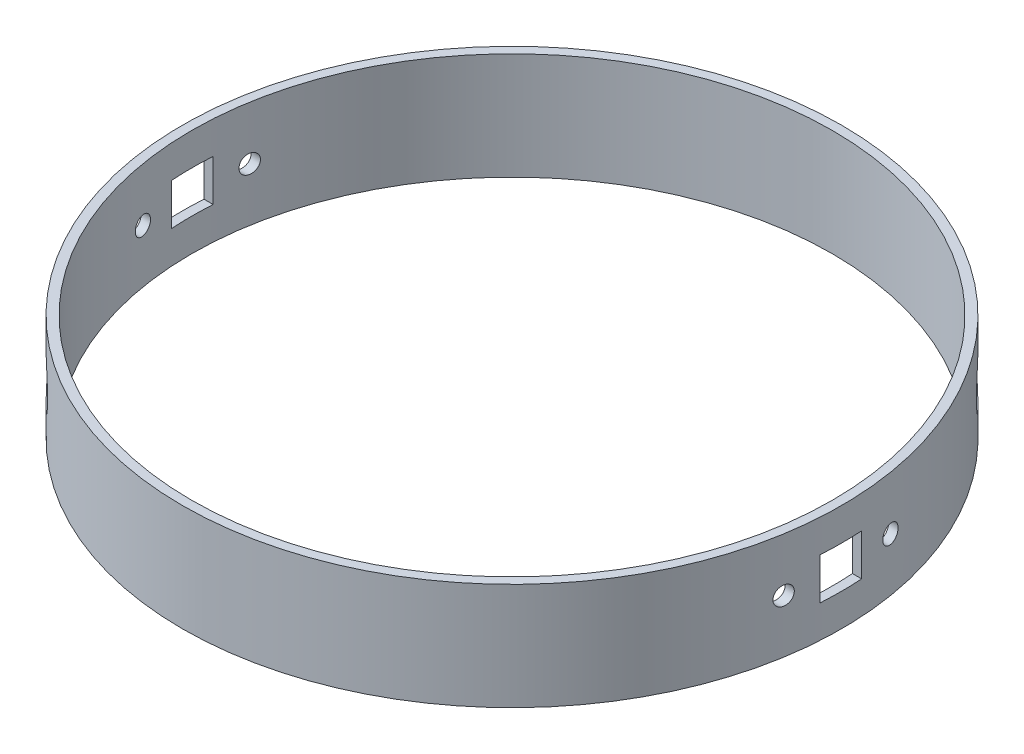
SolidWorks part; units mm, degrees
material "A-Glass Fiber"
ref_plane "Front Plane" through (0, 0, 0) normal (0, 0, 1) x (1, 0, 0)
ref_plane "Top Plane" through (0, 0, 0) normal (0, 1, 0) x (1, 0, 0)
ref_plane "Right Plane" through (0, 0, 0) normal (1, 0, 0) x (0, 0, -1)
sketch "Sketch1" plane through (0, 0, 0) normal (0, 1, 0) x (1, 0, 0)
  circle A0 centre (0, 0) radius 78.359
  circle A1 centre (0, 0) radius 76.1746
  dimension "D1" = 156.718
  dimension "D2" = 152.3492
extrude "Boss-Extrude1" add sketch "Sketch1" along normal blind 25.4
sketch "Sketch2" plane through (0, 0, 0) normal (1, 0, 0) x (0, 0, -1)
  line L0 (-78.359, 0) -> (78.359, 0) construction
  line L7 (0, 12.7) -> (0, 14.52) construction
  line L12 (4.953, 7.747) -> (-4.953, 7.747)
  line L13 (0, 25.4) -> (0, 0) construction
  line L14 (76.1746, 25.4) -> (-76.1746, 25.4) construction
  line L15 (-78.359, 0) -> (78.359, 0)
  line L16 (76.1746, 25.4) -> (-76.1746, 25.4)
  line L17 (-28.7231, 12.7) -> (26.1298, 12.7) construction
  line L25 (4.953, 7.747) -> (4.953, 17.653)
  line L26 (4.953, 17.653) -> (-4.953, 17.653)
  line L27 (-4.953, 7.747) -> (-4.953, 17.653)
  line L28 (4.953, 7.747) -> (-4.953, 17.653) construction
  line L29 (4.953, 17.653) -> (-4.953, 7.747) construction
  circle A0 centre (-12.7, 12.7) radius 2.1831
  circle A1 centre (12.7, 12.7) radius 2.1831
  point P0 (0, 9.85)
  point P14 (0, 3.175)
  point P27 (0, 12.7)
  dimension "D4" = 9.906
  dimension "D8" = 4.3663
  dimension "D1" = 12.7
  dimension "D5" = 9.906
extrude "Cut-Extrude1" cut sketch "Sketch2" along normal through all both and the other way through all contours L25 L12 L27 L26 | A1 | A0
ref_plane "Plane1" through (0, 0, 0) normal (0.9973, 0, 0.0728) x (0, -1, 0)
ref_plane "Plane2" through (0, 12.7, 0) normal (0, 1, 0) x (1, 0, 0)
mirror "Mirror2" about plane through (0, 0, 0) normal (1, 0, 0) of "Cut-Extrude1", "Boss-Extrude1" second plane through (0, 12.7, 0) second plane normal (0, 1, 0)
ref_plane "Plane3" through (0, 0, 0) normal (0.7071, 0, -0.7071) x (-0.7071, 0, -0.7071)
sketch "Sketch3" plane through (0, 0, 0) normal (0.7071, 0, -0.7071) x (-0.7071, 0, -0.7071)
  line L0 (0, 25.4) -> (0, 0) construction
  line L1 (-78.359, 0) -> (78.359, 0) construction
  circle A0 centre (0, 12.7) radius 6.35
  dimension "D1" = 12.7
  dimension "D2" = 12.7
extrude "Cut-Extrude2" cut sketch "Sketch3" against normal through all both and the other way through all
equation "\"Bodytube_OD\" = 6.17in"
equation "\"Bodytube_ID\" = 5.998in"
equation "\"D1@Sketch1\"=\"Bodytube_OD\""
equation "\"D2@Sketch1\"= \"Bodytube_ID\""
equation "\"Camera_Cutout_Width\"=10mm"
equation "\"Camera_Cutout_Height\"=7mm"
equation "\"Fwd_Tube_Length\" = 38.5in"
equation "\"BKHD_Screw_Diam\"= 3.5mm"
equation "\"Fwd_BKHD_From_Top\" = 18in"
equation "\"Shear_Screw_Diameter\" = 0.086in"
equation "\"Shear_Screw_Coupler_Location\" = 4.5in"
equation "\"Motor_OD\" = 4in"
equation "\"Mid_Coupler_Length\" = 13in"
equation "\"Aft_Section_Length\"= 36in"
equation "\"AB_Coupler_OD_Length\"= 1in"
equation "\"AB_Coupling_Section_Length\"= 0.375in"
equation "\"AB_Coupler_Length\"= \"AB_Coupler_OD_Length\" + \"AB_Coupling_Section_Length\" * 2"
equation "\"Cutout_Angle\" = 80"
equation "\"AB_Paddle_Height\" = 0.375in"
equation "\"AB_Coupler_Num_Screws\"= 4"
equation "\"AB_BKHD_Thickness\" = 0.375in"
equation "\"AB_Mount_From_Bottom\" = 23.175in"
equation "\"Num_Cutouts\" = 3"
equation "\"AB_Coupler_OD\"= 6.17in"
equation "\"AB_Coupler_ID\"= 5.75in"
equation "\"AB_Coupler_Surface_Diameter\"= 5.998in"
equation "\"AB_Coupling_Screw_Diameter\"= 0.15748in"
equation "\"AB_Central_Bushing_Length\" = .4724in"
equation "\"Lead_Screw_Dist\" = 3.4in"
equation "\"Lead_Screw_Diam\" = 0.386in"
equation "\"Lead_Screw_Length\" = (\"Mid_Coupler_Length\" + 2*0.375in + 2*.75in)"
equation "\"Paddle_Pin_Offset\" = .25in"
equation "\"Paddle_Pin_Radius\" = 2.25in"
equation "\"SS_Paddle_Pin_Radius\" = 2.25*0.66in"
equation "\"Paddle_Gear_OD\" = 3.2in"
equation "\"Drive_Gear_OD\" = 1.7in"
equation "\"Fin_Thickness\"= .118in"
equation "\"Guiderail_Cutout_Diameter\"= 1.5in"
equation "\"DB9_Hole_Dist\" = 25mm"
equation "\"DB9_Relief_Width\" = 0.47in"
equation "\"DB9_Relief_Hole_Offset\" = 0.09in"
equation "\"Airbrakes_Wire_Hole_Dia\" = .25in"
equation "\"Airbrakes_Wire_Hole_Dist\" = 1.1in"
equation "\"Servo_Gear_Offset\" = 0.5in"
equation "\"FWD_Shear_Screw_Dist\" = 1.5in"
equation "\"Camera_Screw_Dia\" = 0.216535"
equation "\"Camera_Hole_Angle\" = atn ( 2 / 3 * tan ( 12.5deg ) )"
equation "\"Coupler_OD\" = 5.998"
equation "\"Coupler_ID\" = 5.8"
equation "\"Mounting_Bracket_Centerhole_DIA\" = 0.4in"
equation "\"Drive_Gear_Shaft_DIA\" = \"Mounting_Bracket_Centerhole_DIA\" - 0.02in"
equation "\"Drive_Gear_Fillet\" = 0.22in"
equation "\"Drive_Gear_ID\" = 0.62in"
equation "\"Drive_Gear_Offset\" = 0.01in"
